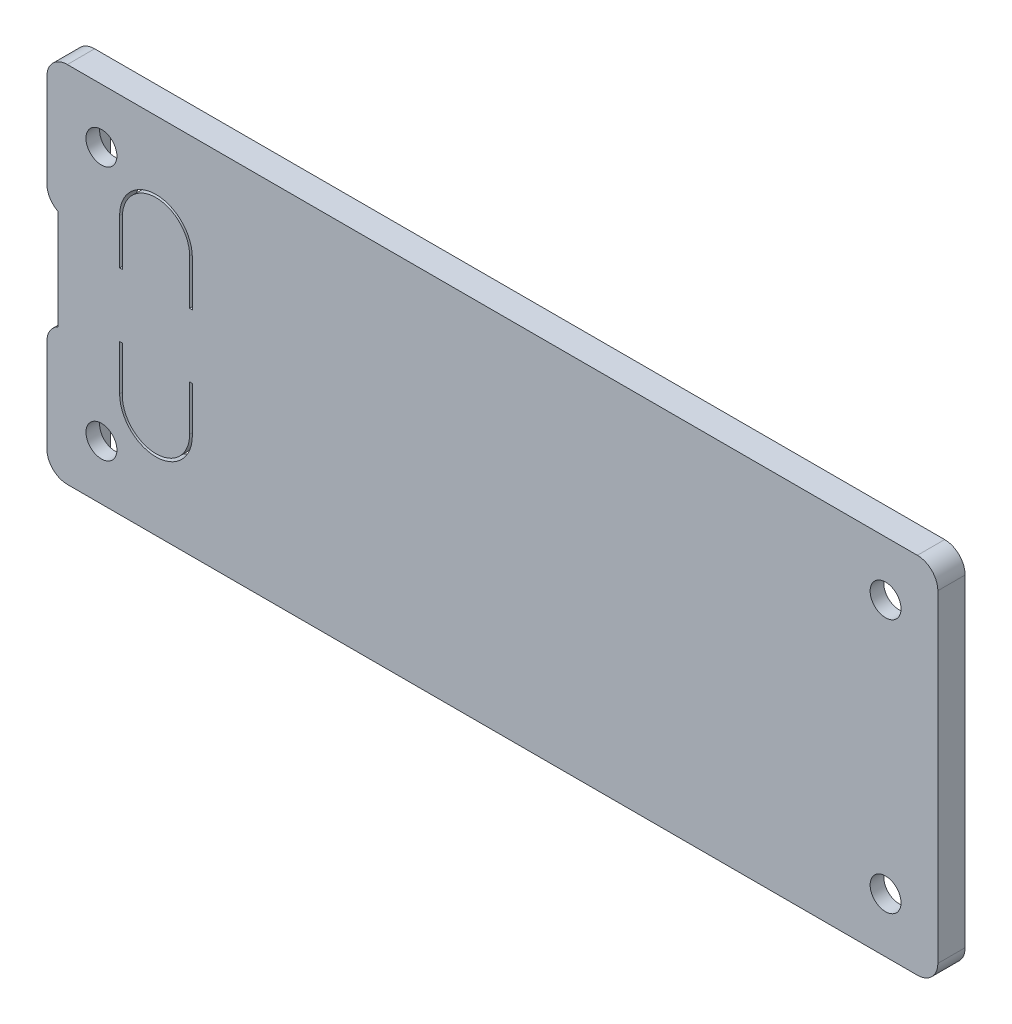
SolidWorks part; units mm, degrees
ref_plane "Front Plane" through (0, 0, 0) normal (0, 0, 1) x (1, 0, 0)
ref_plane "Top Plane" through (0, 0, 0) normal (0, 1, 0) x (1, 0, 0)
ref_plane "Right Plane" through (0, 0, 0) normal (1, 0, 0) x (0, 0, -1)
sketch "Sketch1" plane through (0, 0, 0) normal (0, 0, 1) x (1, 0, 0)
  line L1 (0, 0) -> (98, 0)
  line L2 (0, 0) -> (0, 40)
  line L3 (0, 40) -> (98, 40)
  line L4 (98, 0) -> (98, 40)
  dimension "D1" = 40
  dimension "D2" = 98
extrude "body" add sketch "Sketch1" along normal blind 3
sketch "Sketch2" plane through (0, 0, 3) normal (0, 0, 1) x (1, 0, 0)
  line L0 (0, 40) -> (0, 0) construction
  line L1 (0, 25.25) -> (2.25, 25.25)
  line L2 (0, 25.25) -> (0, 14.75)
  line L3 (0, 14.75) -> (2.25, 14.75)
  line L4 (2.25, 25.25) -> (2.25, 14.75)
  line L5 (0, 20) -> (2.25, 20) construction
  dimension "D1" = 2.25
  dimension "D2" = 10.5
extrude "Cut-Extrude1" cut sketch "Sketch2" against normal through all
fillet "Fillet2" radius 2.25 2 edges at (0, 14.75, 1.5) (0, 25.25, 1.5)
fillet "Fillet1" radius 2.25 4 edges at (0, 0, 1.5) (0, 40, 1.5) (98, 0, 1.5) (98, 40, 1.5)
sketch "Sketch6" plane through (0, 0, 3) normal (0, 0, 1) x (1, 0, 0)
  line L2 (1.25, 25.4844) -> (1.25, 14.5156)
  line L4 (2.25, 25.25) -> (2.25, 14.75)
  arc A0 (0, 27.5) -> (2.25, 25.25) centre (2.25, 27.5) ccw construction
  arc A1 (2.25, 14.75) -> (0, 12.5) centre (2.25, 12.5) ccw construction
  arc A2 (1.25, 25.4844) -> (2.25, 25.25) centre (2.25, 27.5) ccw
  arc A3 (1.25, 14.5156) -> (2.25, 14.75) centre (2.25, 12.5) cw
  dimension "D1" = 1
  dimension "D2" = 2.25
  dimension "D3" = 2.25
extrude "Boss-Extrude4" add sketch "Sketch6" against normal blind 3.7
sketch "Sketch7" plane through (0, 0, 0) normal (0, 0, -1) x (-1, 0, 0)
  line L0 (-2.25, 0) -> (-95.75, 0) construction
  line L1 (-95.75, 40) -> (-2.25, 40) construction
  line L2 (0, 37.75) -> (0, 27.5) construction
  line L4 (-4, 37.75) -> (-95.75, 37.75)
  line L8 (-4, 37.75) -> (-4, 2.25)
  line L9 (-4, 2.25) -> (-95.75, 2.25)
  line L10 (-95.75, 37.75) -> (-95.75, 2.25)
  line L11 (-98, 2.25) -> (-98, 37.75) construction
  point P12 (0, 32.625)
  dimension "D1" = 2.25
  dimension "D2" = 2.25
  dimension "D3" = 2.25
  dimension "D4" = 4
extrude "oled-recess" cut sketch "Sketch7" against normal blind 1.5
sketch "Sketch9" plane through (0, 0, 3) normal (0, 0, 1) x (1, 0, 0)
  line L0 (0, 34) -> (98, 34) construction
  line L1 (0, 37.75) -> (0, 27.5) construction
  line L2 (98, 2.25) -> (98, 37.75) construction
  line L3 (0, 6) -> (98, 6) construction
  line L4 (0, 12.5) -> (0, 2.25) construction
  line L5 (6, 40) -> (6, 0) construction
  line L6 (95.75, 40) -> (2.25, 40) construction
  line L7 (2.25, 0) -> (95.75, 0) construction
  line L8 (92.25, 40) -> (92.25, 0) construction
  line L9 (12, 34) -> (12, 6) construction
  line L14 (8, 28.5) -> (8, 23.5)
  line L15 (16, 28.5) -> (16, 23.5)
  line L16 (15.7, 28.5) -> (15.7, 23.5)
  line L17 (8.3, 28.5) -> (8.3, 23.5)
  line L18 (8, 23.5) -> (8.3, 23.5)
  line L19 (15.7, 23.5) -> (16, 23.5)
  line L20 (16, 23.5) -> (8, 23.5) construction
  line L21 (1.25, 25.4844) -> (1.25, 14.5156) construction
  line L22 (1.25, 20) -> (17.0967, 20) construction
  line L23 (15.7, 16.5) -> (16, 16.5)
  line L24 (8, 16.5) -> (8.3, 16.5)
  line L25 (8.3, 11.5) -> (8.3, 16.5)
  line L26 (15.7, 11.5) -> (15.7, 16.5)
  line L27 (16, 11.5) -> (16, 16.5)
  line L28 (8, 11.5) -> (8, 16.5)
  circle A0 centre (6, 34) radius 1.7
  circle A1 centre (92.25, 34) radius 1.7
  circle A2 centre (6, 6) radius 1.7
  circle A3 centre (92.25, 6) radius 1.7
  arc A4 (8, 28.5) -> (16, 28.5) centre (12, 28.5) cw
  arc A5 (8.3, 28.5) -> (15.7, 28.5) centre (12, 28.5) cw
  arc A6 (8.3, 11.5) -> (15.7, 11.5) centre (12, 11.5) ccw
  arc A7 (8, 11.5) -> (16, 11.5) centre (12, 11.5) ccw
  point P18 (0, 32.625)
  point P19 (92.25, 20)
  point P46 (1.25, 20)
  dimension "D5" = 3.4
  dimension "D6" = 3.4
  dimension "D7" = 3.4
  dimension "D8" = 3.4
  dimension "D16" = 4
  dimension "D1" = 6
  dimension "D2" = 5.75
  dimension "D3" = 14
  dimension "D4" = 14
  dimension "D13" = 6
  dimension "D14" = 5
  dimension "D17" = 8.5
  dimension "D15" = 0.3
extrude "Cut-Extrude5" cut sketch "Sketch9" against normal through all
